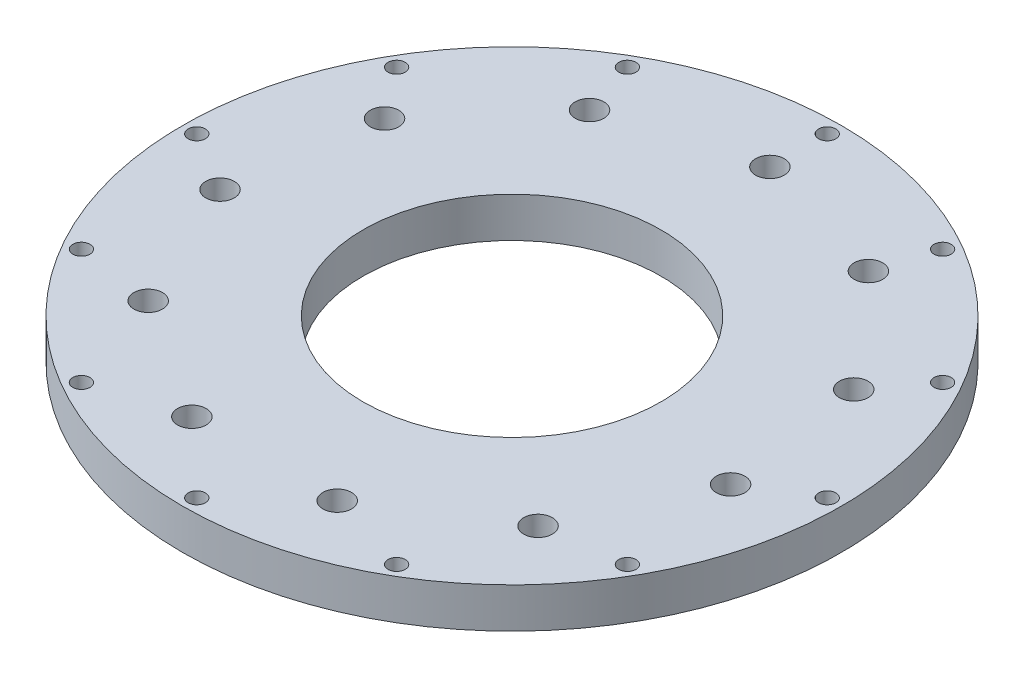
SolidWorks part; units mm, degrees
ref_plane "Front Plane" through (0, 0, 0) normal (0, 0, 1) x (1, 0, 0)
ref_plane "Top Plane" through (0, 0, 0) normal (0, 1, 0) x (1, 0, 0)
ref_plane "Right Plane" through (0, 0, 0) normal (1, 0, 0) x (0, 0, -1)
sketch "Sketch1" plane through (0, 0, 0) normal (0, 1, 0) x (1, 0, 0)
  circle A0 centre (0, 0) radius 57.5
  circle A1 centre (0, 0) radius 55 construction
  circle A2 centre (0, 55) radius 1.5
  circle A3 centre (27.5, 47.6314) radius 1.5
  circle A4 centre (47.6314, 27.5) radius 1.5
  circle A5 centre (55, 0) radius 1.5
  circle A6 centre (47.6314, -27.5) radius 1.5
  circle A7 centre (27.5, -47.6314) radius 1.5
  circle A8 centre (0, -55) radius 1.5
  circle A9 centre (-27.5, -47.6314) radius 1.5
  circle A10 centre (-47.6314, -27.5) radius 1.5
  circle A11 centre (-55, 0) radius 1.5
  circle A12 centre (-47.6314, 27.5) radius 1.5
  circle A13 centre (-27.5, 47.6314) radius 1.5
  circle A14 centre (0, 0) radius 26
  circle A15 centre (0, 0) radius 45 construction
  circle A16 centre (0, 45) radius 2.5
  circle A17 centre (24.3288, 37.8564) radius 2.5
  circle A18 centre (40.9334, 18.6937) radius 2.5
  circle A19 centre (44.542, -6.4042) radius 2.5
  circle A20 centre (34.0087, -29.4687) radius 2.5
  circle A21 centre (12.678, -43.1772) radius 2.5
  circle A22 centre (-12.678, -43.1772) radius 2.5
  circle A23 centre (-34.0087, -29.4687) radius 2.5
  circle A24 centre (-44.542, -6.4042) radius 2.5
  circle A25 centre (-40.9334, 18.6937) radius 2.5
  circle A26 centre (-24.3288, 37.8564) radius 2.5
  point P31 (0, 0)
  point P55 (0, 0)
  dimension "D1" = 115
  dimension "D2" = 110
  dimension "D3" = 3
  dimension "D4" = 52
  dimension "D5" = 90
  dimension "D6" = 5
extrude "Boss-Extrude1" add sketch "Sketch1" along normal blind 7
